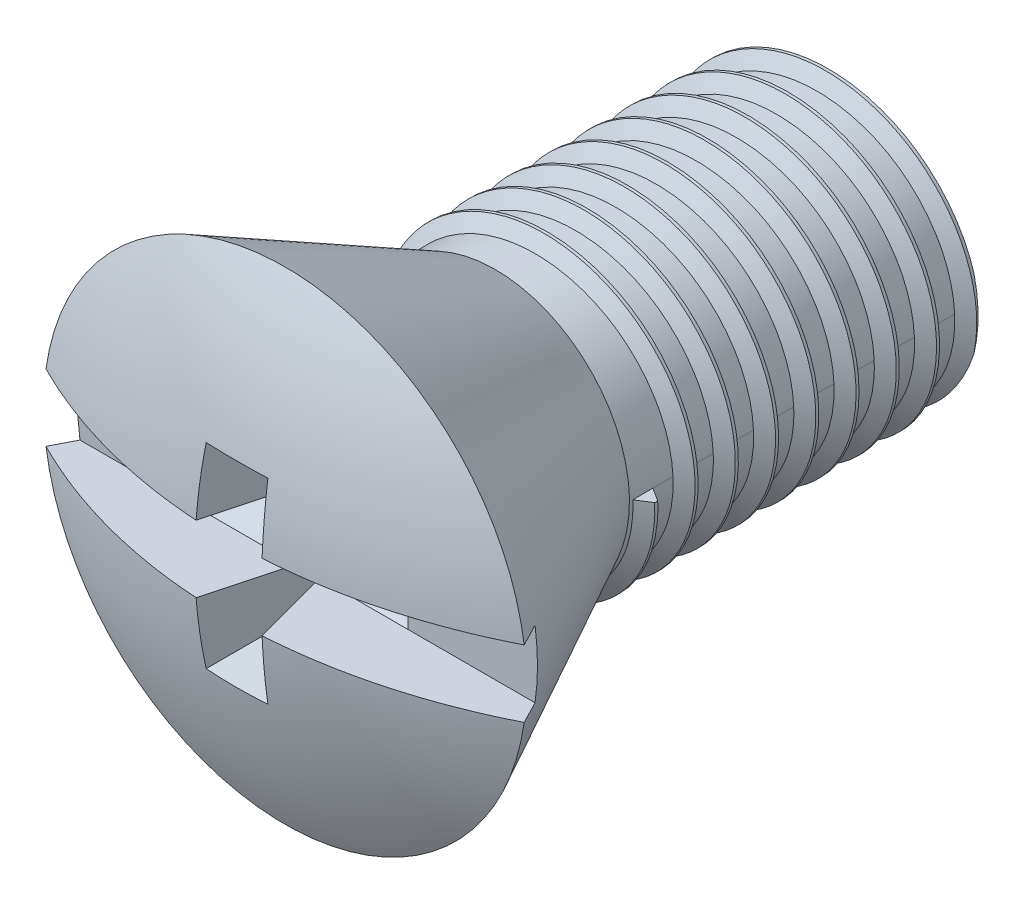
SolidWorks part; units mm, degrees
material "Stainless Steel (ferritic)"
ref_plane "Front" through (0, 0, 0) normal (0, 0, 1) x (1, 0, 0)
ref_plane "Top" through (0, 0, 0) normal (0, 1, 0) x (1, 0, 0)
ref_plane "Right" through (0, 0, 0) normal (1, 0, 0) x (0, 0, -1)
sketch "Sketch2" plane through (0, 0, 0) normal (0, 0, 1) x (1, 0, 0)
  circle A0 centre (0, 0) radius 4.572
  dimension "D1" = 9.144
extrude "Boss-Extrude1" add sketch "Sketch2" along normal blind 5.08
sketch "Sketch3" plane through (0, 0, 0) normal (1, 0, 0) x (0, 0, -1)
  line L0 (0, 0) -> (4.7808, 0) construction
  line L1 (0, -4.572) -> (0, 4.572) construction
  line L2 (0, 2.54) -> (-3.9805, 4.572)
  line L3 (0, 4.572) -> (-5.08, 4.572) construction
  line L4 (-5.08, 4.572) -> (-5.08, -4.572) construction
  line L5 (0, 2.54) -> (0, 4.826)
  line L6 (0, 4.826) -> (-5.334, 4.826)
  line L7 (-5.334, 4.826) -> (-5.334, 0)
  line L8 (-5.334, 0) -> (-5.08, 0)
  line L9 (0, -2.54) -> (-1.4251, -4.572) construction
  line L11 (-5.08, -4.572) -> (0, -4.572) construction
  arc A0 (-3.9805, 4.572) -> (-5.08, 0) centre (4.9756, 0) ccw
  dimension "D1" = 82
  dimension "D2" = 5.08
  dimension "D3" = 5.08
  dimension "D4" = 0.254
  dimension "D5" = 0.254
revolve "Cut-Revolve1" cut sketch "Sketch3" angle 360 about L0
sketch "Sketch4" plane through (0, 0, 0) normal (0, 0, -1) x (-1, 0, 0)
  circle A0 centre (0, 0) radius 2.54
extrude "Boss-Extrude2" add sketch "Sketch4" along normal blind 6.35
sketch "Sketch5" plane through (0, 0, -6.35) normal (0, 0, -1) x (-1, 0, 0)
  circle A0 centre (0, 0) radius 2.54 construction
  circle A1 centre (0, 0) radius 2.54
curve "Helix/Spiral1" pitch 0.762 height 6.096 turns 8
sketch "Sketch6" plane through (0, 0, 0) normal (0, -1, 0) x (0, 0, -1)
  line L8 (0.8255, -2.54) -> (0.4445, -2.54)
  line L9 (0.4445, -2.54) -> (0.6063, -2.794)
  line L10 (0.6063, -2.794) -> (0.6637, -2.794)
  line L11 (0.6637, -2.794) -> (0.8255, -2.54)
  line L12 (0, -2.54) -> (6.35, -2.54) construction
  point P0 (0.635, -2.54)
  dimension "D1" = 0.381
  dimension "D2" = 65
  dimension "D3" = 0.254
sweep "Sweep1" add profiles "Sketch6" path "Helix/Spiral1"
ref_plane "Plane1" through (0, 0, 5.08) normal (0, 0, 1) x (1, 0, 0)
sketch "Sketch7" plane through (0, 0, 5.08) normal (0, 0, 1) x (1, 0, 0)
  line L1 (4.572, -0.635) -> (-4.572, -0.635)
  line L2 (4.572, -0.635) -> (4.572, 0.635)
  line L3 (4.572, 0.635) -> (-4.572, 0.635)
  line L4 (-4.572, -0.635) -> (-4.572, 0.635)
  line L5 (4.572, -0.635) -> (-4.572, 0.635) construction
  line L6 (4.572, 0.635) -> (-4.572, -0.635) construction
  circle A1 centre (0, 0) radius 4.572 construction
  point P0 (0, 0)
  point P6 (-4.572, 0)
  dimension "D1" = 1.27
extrude "Cut-Extrude1" cut sketch "Sketch7" against normal blind 1.524
sketch "Sketch8" plane through (0, 0, 5.08) normal (0, 0, 1) x (1, 0, 0)
  line L1 (-0.635, -1.905) -> (0.635, -1.905)
  line L2 (-0.635, -1.905) -> (-0.635, 1.905)
  line L3 (-0.635, 1.905) -> (0.635, 1.905)
  line L4 (0.635, -1.905) -> (0.635, 1.905)
  line L5 (-0.635, -1.905) -> (0.635, 1.905) construction
  line L6 (-0.635, 1.905) -> (0.635, -1.905) construction
  point P0 (0, 0)
  point P6 (0, 0)
  dimension "D1" = 3.81
  dimension "D2" = 1.27
extrude "Cut-Extrude2" cut sketch "Sketch8" against normal blind 2.794 draft 15 contours L2 L1 L4 L3
sketch "Sketch9" plane through (0, 0, 3.556) normal (0, 0, 1) x (1, 0, 0)
  line L0 (-1.905, -0.635) -> (1.905, -0.635)
  line L1 (-1.905, -0.635) -> (-1.905, 0.635)
  line L2 (-1.905, 0.635) -> (1.905, 0.635)
  line L3 (1.905, -0.635) -> (1.905, 0.635)
  point P4 (0, -0.635)
  point P7 (1.905, 0)
  dimension "D1" = 1.27
  dimension "D2" = 3.81
extrude "Cut-Extrude3" cut sketch "Sketch9" against normal blind 2.54 draft 20
